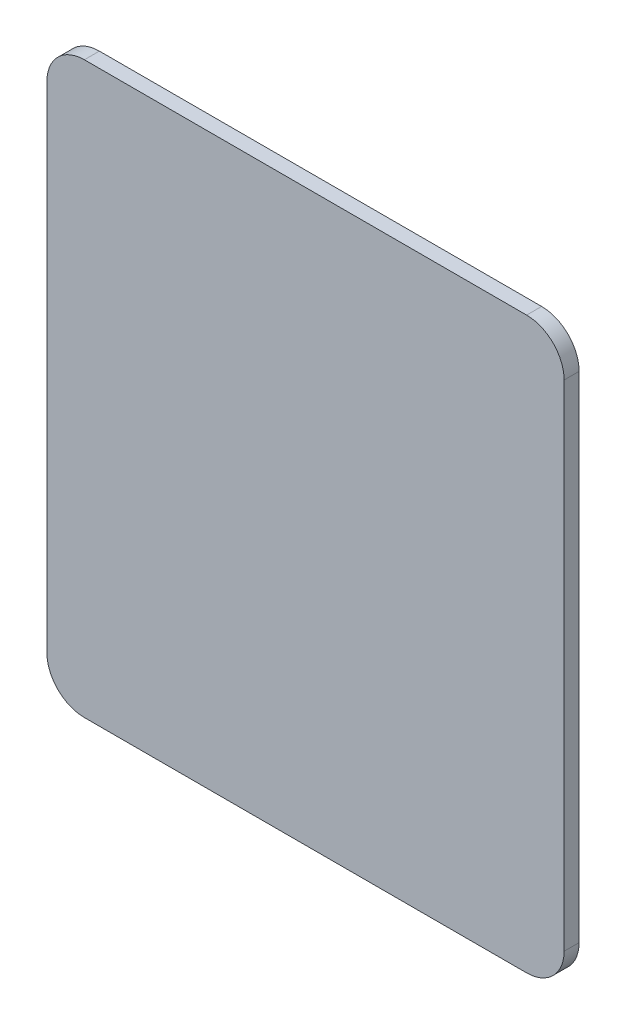
SolidWorks part; units mm, degrees
ref_plane "Plan de face" through (0, 0, 0) normal (0, 0, 1) x (1, 0, 0)
ref_plane "Plan de dessus" through (0, 0, 0) normal (0, 1, 0) x (1, 0, 0)
ref_plane "Plan de droite" through (0, 0, 0) normal (1, 0, 0) x (0, 0, -1)
sketch "Esquisse1" plane through (0, 0, 0) normal (0, 0, 1) x (1, 0, 0)
  line L1 (-29.5, -38) -> (29.5, -38)
  line L2 (-34.5, -33) -> (-34.5, 33)
  line L3 (-29.5, 38) -> (29.5, 38)
  line L4 (34.5, -33) -> (34.5, 33)
  line L5 (-34.5, -38) -> (34.5, 38) construction
  line L6 (-34.5, 38) -> (34.5, -38) construction
  arc A0 (34.5, 33) -> (29.5, 38) centre (29.5, 33) ccw
  arc A1 (29.5, -38) -> (34.5, -33) centre (29.5, -33) ccw
  arc A2 (-34.5, -33) -> (-29.5, -38) centre (-29.5, -33) ccw
  arc A3 (-34.5, 33) -> (-29.5, 38) centre (-29.5, 33) cw
  point P0 (0, 0)
  dimension "D3" = 5
  dimension "D1" = 69
  dimension "D2" = 76
extrude "Boss.-Extru.1" add sketch "Esquisse1" against normal blind 2
